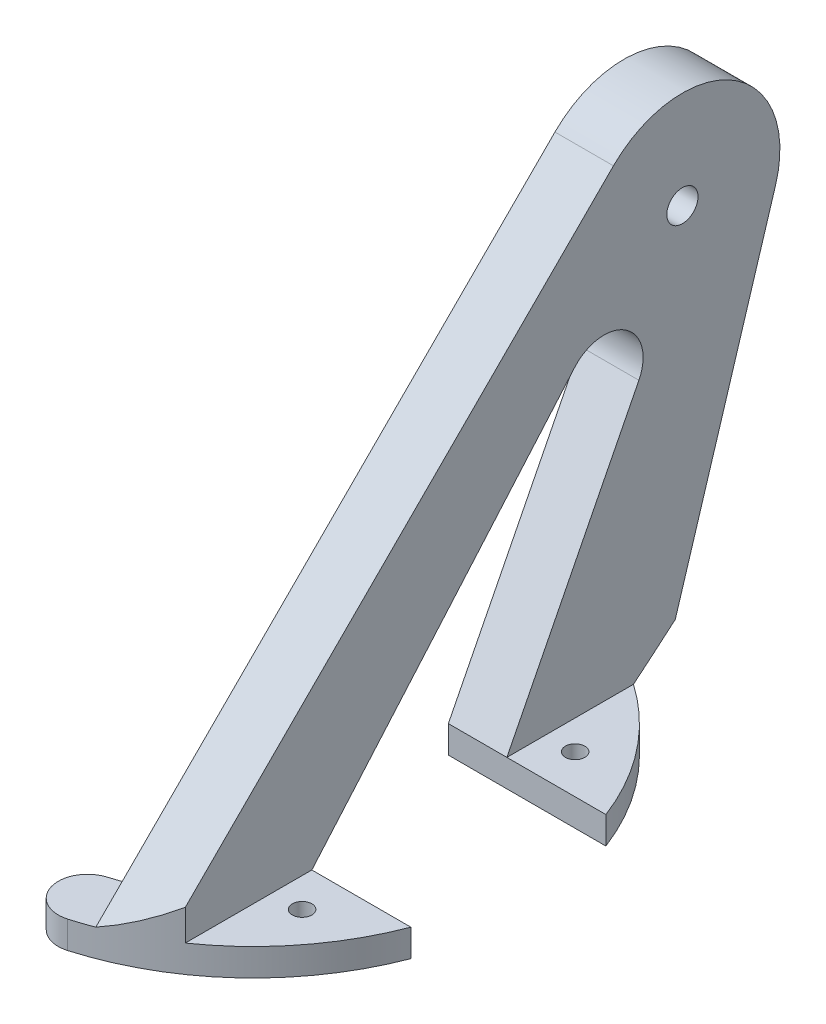
SolidWorks part; units mm, degrees
ref_plane "Front Plane" through (0, 0, 0) normal (0, 0, 1) x (1, 0, 0)
ref_plane "Top Plane" through (0, 0, 0) normal (0, 1, 0) x (1, 0, 0)
ref_plane "Right Plane" through (0, 0, 0) normal (1, 0, 0) x (0, 0, -1)
sketch "Sketch1" plane through (0, 0, 0) normal (0, 1, 0) x (1, 0, 0)
  line L0 (25, 65.3835) -> (25, -65.3835)
  line L1 (40, 57.4456) -> (40, -57.4456) construction
  line L2 (25, 25) -> (65.3835, 25)
  line L3 (25, -25) -> (65.3835, -25)
  circle A0 centre (0, 0) radius 20 construction
  circle A1 centre (0, 0) radius 70
  circle A2 centre (0, 0) radius 30 construction
  dimension "D1" = 40
  dimension "D2" = 140
  dimension "D4" = 60
  dimension "D3" = 25
  dimension "D5" = 15
  dimension "D6" = 25
  dimension "D7" = 25
extrude "Boss-Extrude1" add sketch "Sketch1" against normal blind 7 contours L2 A1 L0 | L0 A1 L3 region at (40.3471, 0, -40.3471) region at (40.3471, 0, 40.3471)
sketch "Sketch2" plane through (25, 0, 0) normal (-1, 0, 0) x (0, 0, 1)
  line L0 (0, 0) -> (-70, 0) construction
  line L1 (-70, 0) -> (-70, 100) construction
  line L2 (-65.3835, 0) -> (-93.8942, 92.6469)
  line L3 (65.3835, 0) -> (-52.3244, 117.6798)
  line L4 (-70, 100) -> (0, 0) construction
  line L5 (25, 0) -> (-42.3661, 77.8695)
  line L6 (-25, 0) -> (-58.8492, 66.8072)
  line L7 (-65.3835, 0) -> (-25, 0)
  line L8 (25, 0) -> (65.3835, 0)
  arc A0 (-52.3244, 117.6798) -> (-93.8942, 92.6469) centre (-70, 100) ccw
  arc A1 (-42.3661, 77.8695) -> (-58.8492, 66.8072) centre (-49.9288, 71.3269) ccw
  dimension "D1" = 70
  dimension "D3" = 50
  dimension "D4" = 20
  dimension "D2" = 100
extrude "Boss-Extrude2" add sketch "Sketch2" against normal blind 15
sketch "Sketch3" plane through (0, 0, 0) normal (0, 1, 0) x (1, 0, 0)
  circle A0 centre (0, 0) radius 70
  circle A1 centre (0, 0) radius 92.4862
extrude "Cut-Extrude2" cut sketch "Sketch3" along normal blind 10
chamfer "Chamfer2" distance 10 angle 45 1 edges at (32.7414, 10, -61.8708)
sketch "Sketch4" plane through (25, 0, 0) normal (-1, 0, 0) x (0, 0, 1)
  circle A0 centre (-70, 100) radius 4
  dimension "D1" = 8
extrude "Cut-Extrude3" cut sketch "Sketch4" against normal through all
sketch "Sketch5" plane through (25, 0, 0) normal (-1, 0, 0) x (0, 0, 1)
  circle A0 centre (-70, 100) radius 11
  dimension "D1" = 22
extrude "Cut-Extrude4" cut sketch "Sketch5" against normal blind 5
sketch "Sketch6" plane through (0, 0, 0) normal (0, 1, 0) x (1, 0, 0)
  line L0 (-22.2109, 0) -> (22.2109, 0) construction
  line L1 (0, -72.6) -> (0, 72.6) construction
  circle A0 centre (0, 0) radius 70 construction
  circle A1 centre (47.5, -35) radius 5 construction
  circle A2 centre (47.5, 35) radius 5 construction
  circle A3 centre (47.5, 35) radius 2.5
  circle A4 centre (47.5, -35) radius 2.5
  dimension "D1" = 10
  dimension "D3" = 47.5
  dimension "D4" = 5
  dimension "D5" = 5
  dimension "D2" = 35
extrude "Cut-Extrude5" cut sketch "Sketch6" against normal through all
sketch "Sketch7" plane through (0, 0, 0) normal (0, 1, 0) x (1, 0, 0)
  line L0 (25, -65.3835) -> (25, 52.3244) construction
  line L1 (25.1277, -48.9244) -> (25, -65.3835)
  circle A0 centre (0, 0) radius 70
  arc A1 (15.4, -52.8) -> (19.6, -67.2) centre (17.5, -60) ccw
  circle A2 centre (0, 0) radius 55
  point P12 (25.1277, -48.9244)
  dimension "D1" = 15
  dimension "D2" = 140
extrude "Boss-Extrude3" add sketch "Sketch7" against normal blind 7 contours A2 A1 A0 L1 region at (18.3574, 0, 59.1859)
